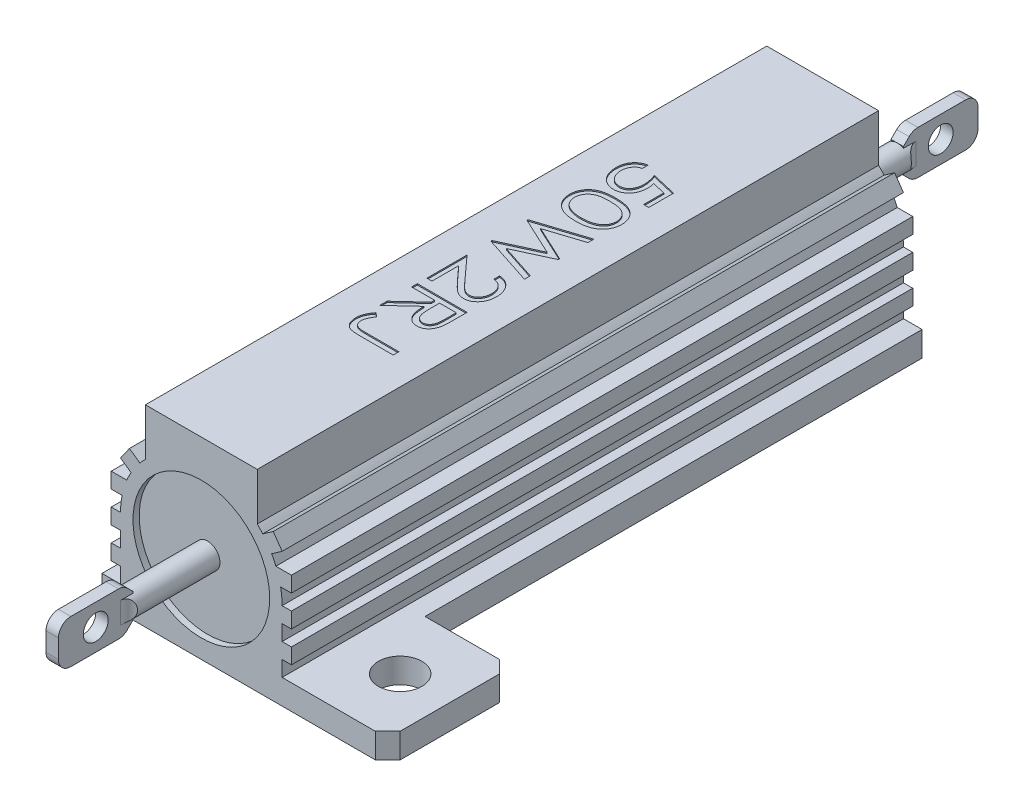
SolidWorks part; units mm, degrees
ref_plane "Front Plane" through (0, 0, 0) normal (0, 0, 1) x (1, 0, 0)
ref_plane "Top Plane" through (0, 0, 0) normal (0, 1, 0) x (1, 0, 0)
ref_plane "Right Plane" through (0, 0, 0) normal (1, 0, 0) x (0, 0, -1)
sketch "Sketch1" plane through (0, 0, 0) normal (0, 0, 1) x (1, 0, 0)
  line L0 (-6.5, -7) -> (6.5, -7)
  line L1 (-4.5, 8.5) -> (4.5, 8.5)
  line L2 (-4.5, 8.5) -> (-4.5, 0)
  line L3 (-4.5, 0) -> (4.5, 0)
  line L4 (4.5, 8.5) -> (4.5, 0)
  line L5 (6.5, -5) -> (6.5, -3.75)
  line L6 (-6.5, -5) -> (-6.5, -3.75)
  line L7 (-7.25, -2.5) -> (-7.25, -1.25) construction
  line L8 (-6.5, -7) -> (-8, -7)
  line L10 (-6.5, -5) -> (-8, -5)
  line L11 (-8, -7) -> (-8, -5)
  line L12 (-6.5, -3.75) -> (-7.25, -3.75)
  line L14 (-6.5, -2.5) -> (-7.25, -2.5)
  line L15 (-7.25, -3.75) -> (-7.25, -2.5)
  line L16 (-6.5, -1.25) -> (-7.25, -1.25)
  line L18 (-6.5, 0) -> (-7.25, 0)
  line L19 (-7.25, -1.25) -> (-7.25, 0)
  line L20 (-6.3787, 1.25) -> (-7.25, 1.25)
  line L22 (-6, 2.5) -> (-7.25, 2.5)
  line L23 (-7.25, 1.25) -> (-7.25, 2.5)
  line L24 (-7.25, 0) -> (-7.25, 1.25) construction
  line L25 (-7.25, -3.75) -> (-7.25, -5) construction
  line L26 (-5.6583, 3.199) -> (-6.5021, 3.7899)
  line L27 (-6.5021, 3.7899) -> (-5.7852, 4.8138)
  line L28 (-5.7852, 4.8138) -> (-4.9413, 4.2229)
  line L29 (0, 0) -> (-6.1436, 4.3018) construction
  line L30 (0, 8.5) -> (0, 50008.5) construction
  line L31 (6.5, -5) -> (8, -5)
  line L32 (8, -7) -> (8, -5)
  line L33 (6.5, -7) -> (8, -7)
  line L35 (6.5, -2.5) -> (7.25, -2.5)
  line L36 (7.25, -3.75) -> (7.25, -2.5)
  line L37 (6.5, -3.75) -> (7.25, -3.75)
  line L39 (6.5, -1.25) -> (7.25, -1.25)
  line L40 (7.25, -1.25) -> (7.25, 0)
  line L41 (6.5, 0) -> (7.25, 0)
  line L42 (7.25, 1.25) -> (7.25, 2.5)
  line L43 (6, 2.5) -> (7.25, 2.5)
  line L44 (6.3787, 1.25) -> (7.25, 1.25)
  line L45 (5.7852, 4.8138) -> (4.9413, 4.2229)
  line L46 (6.5021, 3.7899) -> (5.7852, 4.8138)
  line L47 (5.6583, 3.199) -> (6.5021, 3.7899)
  line L48 (6.5, -2.5) -> (6.5, -1.25)
  line L49 (-6.5, -2.5) -> (-6.5, -1.25)
  circle A0 centre (0, 0) radius 5.5
  circle A1 centre (0, 0) radius 1
  arc A2 (6.5, 0) -> (6.3787, 1.25) centre (0, 0) ccw
  arc A3 (-6.3787, 1.25) -> (-6.5, 0) centre (0, 0) ccw
  arc A4 (-5.6583, 3.199) -> (-6, 2.5) centre (0, 0) ccw
  arc A5 (4.9413, 4.2229) -> (-4.9413, 4.2229) centre (0, 0) ccw
  arc A6 (6, 2.5) -> (5.6583, 3.199) centre (0, 0) ccw
  dimension "D1" = 11
  dimension "D3" = 2
  dimension "D2" = 13
  dimension "D4" = 8.5
  dimension "D5" = 9
  dimension "D6" = 7
  dimension "D7" = 2
  dimension "D8" = 8
  dimension "D9" = 7.25
  dimension "D10" = 1.25
  dimension "D11" = 1.25
  dimension "D12" = 7.5
  dimension "D13" = 35
extrude "Boss-Extrude1" add sketch "Sketch1" along normal mid plane 50 contours L43 A6 L47 L46 L45 A5 L4 A0 L2 L28 L27 L26 A4 L22 L23 L20 A3 L18 L19 L16 L49 L14 L15 L12 L6 L10 L11 L8 L0 L33 L32 L31 L5 L37 L36 L35 L48 L39 L40 L41 A2 L44 L42 | L4 A5 L2 A0 | A5 L4 L1 L2 region at (-7.25, -6.8011, 0) region at (0, 6.404, 0) region at (0, 7.1636, 0)
sketch "Sketch3" plane through (0, -7, 0) normal (0, -1, 0) x (1, 0, 0)
  line L0 (15, 20) -> (11, 20) construction
  line L1 (8, 25) -> (15, 25)
  line L2 (8, 25) -> (8, 15)
  line L3 (8, 15) -> (15, 15)
  line L4 (15, 25) -> (15, 15)
  line L5 (-8, -25) -> (-15, -25)
  line L6 (-8, -25) -> (-8, -15)
  line L7 (-8, -15) -> (-15, -15)
  line L8 (-15, -25) -> (-15, -15)
  line L9 (-11, -20) -> (-15, -20) construction
  circle A0 centre (11, 20) radius 1.75
  circle A1 centre (-11, -20) radius 1.75
  dimension "D3" = 4
  dimension "D4" = 3.5
  dimension "D1" = 10
  dimension "D2" = 7
extrude "Boss-Extrude5" add sketch "Sketch3" against normal up to surface (2 mm away) up to face at (7.25, -5, 0)
chamfer "Chamfer1" distance 1 angle 45 4 edges at (-15, -6, -15) (-15, -6, -25) (15, -6, 15) (15, -6, 25)
extrude "Boss-Extrude2" add sketch "Sketch1<3>" along normal mid plane 49 separate body contours A1 L3 L2 A0 L4 | A1 L3 L4 A0 L2 region at (0, 2.5232, 0) region at (0, -2.0914, 0)
sketch "Sketch1<3>" plane through (0, 0, 0) normal (0, 0, 1) x (1, 0, 0) same geometry as "Sketch1"
extrude "Boss-Extrude3" add sketch "Sketch1<4>" along normal mid plane 62 separate body contours L3 A1 | L3 A1 region at (0, 0.4244, 0) region at (0, -0.4244, 0)
sketch "Sketch1<4>" plane through (0, 0, 0) normal (0, 0, 1) x (1, 0, 0) same geometry as "Sketch1"
sketch "Sketch2" plane through (0, 0, 0) normal (1, 0, 0) x (0, 0, -1)
  line L0 (-31, 1) -> (-31, -1) construction
  line L1 (-31.75, -1.75) -> (-37, -1.75)
  line L2 (-31, -1) -> (-31, 1)
  line L3 (-31.75, 1.75) -> (-37, 1.75)
  line L4 (-37, -1.75) -> (-37, 1.75)
  line L5 (-31, 1) -> (-31.75, 1.75)
  line L6 (31, 1) -> (-31, 1) construction
  line L7 (-31, -1) -> (-31.75, -1.75)
  line L8 (-31, -1) -> (31, -1) construction
  circle A0 centre (-34, 0) radius 1
  point P0 (-37, 0)
  dimension "D3" = 3
  dimension "D4" = 2
  dimension "D1" = 6
  dimension "D2" = 3.5
  dimension "D5" = 135
extrude "Boss-Extrude4" add sketch "Sketch2" along normal mid plane 1
mirror "Mirror1" about plane through (0, 0, 0) normal (0, 0, 1) of "Boss-Extrude4"
fillet "Fillet1" radius 1 12 edges at (0, -1.75, 31.75) (0, 1.75, 31.75) (-0.5, 0, 31) (0.5, 0, 31) (0, -1.75, 37) (0, 1.75, 37) (0, 1.75, -37) (0, -1.75, -37) (0, -1.75, -31.75) (0, 1.75, -31.75) (-0.5, 0, -31) (0.5, 0, -31)
sketch "Sketch4" plane through (0, 8.5, 0) normal (0, 1, 0) x (1, 0, 0)
  line L0 (-2, 25) -> (-2, -25) construction
  line L1 (-4.5, -25) -> (4.5, -25) construction
  line L2 (-4.5, 25) -> (4.5, 25) construction
  text T0 "50W2RJ" font "Century Gothic" height 4
  point P0 (0, 0)
  point P3 (-2, 0)
  dimension "D1" = 2
extrude "Cut-Extrude1" cut sketch "Sketch4" against normal blind 0.1
